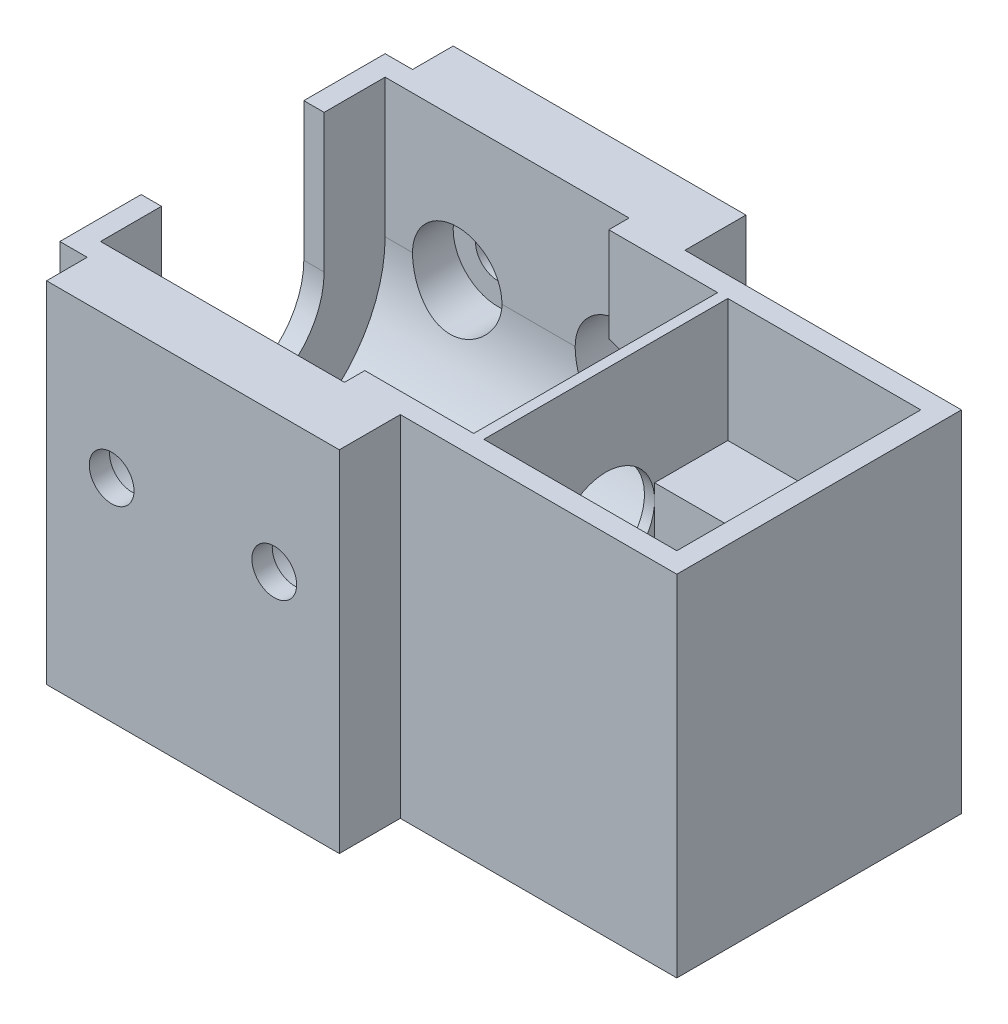
SolidWorks part; units mm, degrees
ref_plane "Front Plane" through (0, 0, 0) normal (0, 0, 1) x (1, 0, 0)
ref_plane "Top Plane" through (0, 0, 0) normal (0, 1, 0) x (1, 0, 0)
ref_plane "Right Plane" through (0, 0, 0) normal (1, 0, 0) x (0, 0, -1)
sketch "Sketch1" plane through (0, 0, 0) normal (0, 0, 1) x (1, 0, 0)
  line L1 (-76.2, -50.8) -> (40.64, -50.8)
  line L2 (-76.2, -50.8) -> (-76.2, 0)
  line L3 (-76.2, 0) -> (40.64, 0)
  line L4 (40.64, -50.8) -> (40.64, 0)
  line L5 (-76.2, -50.8) -> (40.64, 0) construction
  line L6 (-76.2, 0) -> (40.64, -50.8) construction
  point P0 (0, 0)
  dimension "D1" = 116.84
  dimension "D2" = 50.8
  dimension "D3" = 76.2
extrude "Boss-Extrude1" add sketch "Sketch1" along normal mid plane 63.5
sketch "Sketch2" plane through (0, 0, 0) normal (0, 0, 1) x (1, 0, 0)
  line L0 (-152.4829, -25.4) -> (6.8382, -25.4) construction
  line L1 (-49.3609, -3.175) -> (-49.3609, -12.7)
  line L2 (40.64, 0) -> (-76.2, 0) construction
  line L3 (40.64, 0) -> (-76.2, 0) construction
  line L4 (-11.2609, -3.175) -> (-11.2609, -6.35)
  line L5 (-11.2609, -25.4) -> (-11.2609, -3.175) construction
  line L6 (-128.4172, -25.4) -> (-157.8092, -25.4)
  line L7 (6.8382, -25.4) -> (40.64, -25.4)
  line L8 (-607.3619, -25.4) -> (6.8382, -25.4) construction
  line L9 (-49.3609, -3.175) -> (-11.2609, -3.175)
  line L10 (6.8382, -25.4) -> (-128.4172, -25.4)
  line L11 (-11.2609, -6.35) -> (5.7391, -6.35)
  line L12 (5.7391, -6.35) -> (5.7391, -17.78)
  line L13 (5.7391, -17.78) -> (23.7391, -17.78)
  line L14 (-49.3609, -12.7) -> (-220.2024, -12.7)
  line L15 (-220.2024, -12.7) -> (-220.2024, -25.4)
  line L16 (-220.2024, -25.4) -> (-157.8092, -25.4)
  line L17 (23.7391, -17.78) -> (23.7391, -25.4) construction
  line L18 (23.7391, -17.78) -> (40.64, -17.78)
  line L19 (40.64, -50.8) -> (40.64, 0) construction
  line L20 (40.64, -17.78) -> (40.64, -25.4)
  line L21 (-76.2, 0) -> (-76.2, -50.8) construction
  point P23 (-11.2609, -25.4)
  dimension "D1" = 22.225
  dimension "D2" = 38.1
  dimension "D3" = 25.4
  dimension "D4" = 35
  dimension "D5" = 7.62
  dimension "D6" = 3.175
  dimension "D7" = 26.8391
  dimension "D8" = 18
  dimension "D9" = 12.7
revolve "Cut-Revolve1" cut sketch "Sketch2" angle 360 about L0
sketch "Sketch38" plane through (40.64, 0, 0) normal (1, 0, 0) x (0, 0, -1)
  line L1 (-10, -35.4) -> (10, -35.4)
  line L2 (-10, -35.4) -> (-10, -15.4)
  line L3 (-10, -15.4) -> (10, -15.4)
  line L4 (10, -35.4) -> (10, -15.4)
  line L5 (-10, -35.4) -> (10, -15.4) construction
  line L6 (-10, -15.4) -> (10, -35.4) construction
  point P0 (0, -25.4)
  point P1 (0, -25.4)
  dimension "D1" = 20
  dimension "D2" = 20
extrude "Cut-Extrude33" cut sketch "Sketch38" against normal offset from surface (33.3134 mm away) 1.5875 up to face at (5.7391, -44.45, 0)
sketch "Sketch37" plane through (40.64, 0, 0) normal (1, 0, 0) x (0, 0, -1)
  line L0 (31.75, -50.8) -> (31.75, 0) construction
  line L1 (-31.75, 0) -> (31.75, 0)
  line L2 (-31.75, 0) -> (-31.75, -25.4)
  line L3 (-31.75, -25.4) -> (31.75, -25.4)
  line L4 (31.75, 0) -> (31.75, -25.4)
  line L5 (10, -35.4) -> (10, -15.4) construction
  point P7 (0, -25.4)
  point P11 (0, 0)
  point P14 (10, -25.4)
extrude "Cut-Extrude32" cut sketch "Sketch37" against normal through all
sketch "Sketch39" plane through (0, -25.4, 0) normal (0, 1, 0) x (1, 0, 0)
  line L10 (-76.2, 12.7) -> (-49.3609, 12.7)
  line L11 (-49.3609, 12.7) -> (-49.3609, 22.225)
  line L12 (-49.3609, 22.225) -> (-11.2609, 22.225)
  line L13 (-11.2609, 22.225) -> (-11.2609, 19.05)
  line L14 (-11.2609, 19.05) -> (5.7391, 19.05)
  line L15 (5.7391, 19.05) -> (5.7391, 7.62)
  line L16 (5.7391, 19.05) -> (5.7391, 7.62)
  line L17 (40.64, 10) -> (40.64, 31.75)
  line L18 (40.64, 31.75) -> (-76.2, 31.75)
  line L19 (-76.2, 31.75) -> (-76.2, 12.7)
  line L20 (-76.2, 12.7) -> (-49.3609, 12.7)
  line L21 (-49.3609, 12.7) -> (-49.3609, 22.225)
  line L22 (-49.3609, 22.225) -> (-11.2609, 22.225)
  line L23 (-11.2609, 22.225) -> (-11.2609, 19.05)
  line L24 (-11.2609, 19.05) -> (5.7391, 19.05)
  line L25 (7.3266, 10) -> (40.64, 10)
  line L26 (7.3266, 10) -> (40.64, 10)
  line L27 (40.64, 10) -> (40.64, 31.75)
  line L28 (40.64, 31.75) -> (-76.2, 31.75)
  line L29 (-76.2, 31.75) -> (-76.2, 12.7)
  line L30 (-49.3609, -12.7) -> (-76.2, -12.7)
  line L31 (-76.2, -12.7) -> (-76.2, -31.75)
  line L32 (-76.2, -31.75) -> (40.64, -31.75)
  line L33 (40.64, -31.75) -> (40.64, -10)
  line L34 (40.64, -10) -> (7.3266, -10)
  line L35 (40.64, -10) -> (7.3266, -10)
  line L36 (5.7391, -19.05) -> (-11.2609, -19.05)
  line L37 (-11.2609, -19.05) -> (-11.2609, -22.225)
  line L38 (-11.2609, -22.225) -> (-49.3609, -22.225)
  line L39 (-49.3609, -22.225) -> (-49.3609, -12.7)
  line L40 (-49.3609, -12.7) -> (-76.2, -12.7)
  line L41 (-76.2, -12.7) -> (-76.2, -31.75)
  line L42 (-76.2, -31.75) -> (40.64, -31.75)
  line L43 (40.64, -31.75) -> (40.64, -10)
  line L44 (5.7391, -7.62) -> (5.7391, -19.05)
  line L45 (5.7391, -7.62) -> (5.7391, -19.05)
  line L46 (5.7391, -19.05) -> (-11.2609, -19.05)
  line L47 (-11.2609, -19.05) -> (-11.2609, -22.225)
  line L48 (-11.2609, -22.225) -> (-49.3609, -22.225)
  line L49 (-49.3609, -22.225) -> (-49.3609, -12.7)
  line L52 (5.7391, 7.62) -> (7.3266, 7.62)
  line L53 (5.7391, 7.62) -> (7.3266, 7.62)
  line L54 (7.3266, 7.62) -> (7.3266, 10)
  line L55 (7.3266, 7.62) -> (7.3266, 10)
  line L56 (7.3266, -10) -> (7.3266, -7.62)
  line L57 (7.3266, -10) -> (7.3266, -7.62)
  line L58 (7.3266, -7.62) -> (5.7391, -7.62)
  line L59 (7.3266, -7.62) -> (5.7391, -7.62)
  dimension "D1" = 0
  dimension "D2" = 0
extrude "Boss-Extrude5" add sketch "Sketch39" along normal blind 25.4
sketch "Sketch40" plane through (0, 0, 0) normal (0, 1, 0) x (1, 0, 0)
  line L0 (7.3266, 10) -> (40.64, 10) construction
  line L1 (23.7391, 10) -> (40.64, 10)
  line L2 (23.7391, 10) -> (23.7391, -10)
  line L3 (23.7391, -10) -> (40.64, -10)
  line L4 (40.64, 10) -> (40.64, -10)
  line L6 (-11.2609, 22.225) -> (-11.2609, 19.05) construction
  dimension "D1" = 35
extrude "Boss-Extrude6" add sketch "Sketch40" against normal up to next
sketch "Sketch41" plane through (0, 0, 0) normal (0, 1, 0) x (1, 0, 0)
  line L2 (-76.2, 12.7) -> (-76.2, -12.7) construction
  circle A0 centre (-57.15, 0) radius 3.1134
  circle A1 centre (-31.75, 0) radius 3.1134
  circle A2 centre (-6.35, 0) radius 3.1134
  dimension "D1" = 19.05
extrude "Cut-Extrude34" cut sketch "Sketch41" against normal through all
ref_plane "Plane_Mid" through (0, -25.4, 0) normal (0, 1, 0) x (1, 0, 0)
ref_axis "Axis1" through (7.3266, -25.4, 0) along (-1, 0, 0)
sketch "Sketch42" plane through (0, 0, 0) normal (0, 0, 1) x (1, 0, 0)
  line L0 (1.7462, -25.4) -> (-1.7462, -25.4) construction
  line L1 (-76.2, 0) -> (-76.2, -25.4) construction
  circle A0 centre (-38.1, -25.4) radius 3.4925
  circle A1 centre (-12.7, -25.4) radius 3.4925
  dimension "D1" = 6.985
  dimension "D2" = 38.1
extrude "Cut-Extrude35" cut sketch "Sketch42" against normal through all both and the other way through all
sketch "Sketch43" plane through (0, 0, 0) normal (0, 0, 1) x (1, 0, 0)
  circle A0 centre (-38.1, -25.4) radius 6.985
  circle A1 centre (-12.7, -25.4) radius 6.985
  dimension "D1" = 13.97
extrude "Cut-Extrude36" cut sketch "Sketch43" against normal offset from surface (28.575 mm away) 3.175 up to face at (-9.2075, -25.4, -31.75)
extrude "Cut-Extrude37" cut sketch "Sketch43<2>" along normal offset from surface (28.575 mm away) 3.175 up to face at (-9.2075, -25.4, 31.75)
sketch "Sketch43<2>" plane through (0, 0, 0) normal (0, 0, 1) x (1, 0, 0) same geometry as "Sketch43"
sketch "Sketch44" plane through (0, 0, 0) normal (0, 1, 0) x (1, 0, 0)
  line L0 (5.7391, -19.05) -> (-11.2609, -19.05) construction
  line L1 (7.3266, 19.05) -> (23.2391, 19.05)
  line L2 (7.3266, 19.05) -> (7.3266, -19.05)
  line L3 (7.3266, -19.05) -> (23.2391, -19.05)
  line L4 (23.2391, 19.05) -> (23.2391, -19.05)
  line L5 (-11.2609, 19.05) -> (5.7391, 19.05) construction
  line L6 (7.3266, 7.62) -> (7.3266, 10) construction
  line L7 (23.7391, 10) -> (23.7391, -10) construction
  dimension "D1" = 0.5
extrude "Cut-Extrude38" cut sketch "Sketch44" against normal up to surface (35.4 mm away) up to face at (15.5329, -35.4, 0)
sketch "Sketch45" plane through (0, 0, 0) normal (0, 0, 1) x (1, 0, 0)
  line L0 (40.64, 0) -> (-76.2, 0) construction
  line L2 (37.465, 0) -> (23.2391, 0)
  line L4 (37.465, 0) -> (37.465, -15.4)
  line L5 (37.465, -15.4) -> (23.2391, -15.4)
  line L8 (23.2391, 0) -> (23.2391, -15.4)
  line L9 (40.64, -50.8) -> (40.64, 0) construction
  line L10 (23.2391, -35.4) -> (23.2391, 0) construction
  line L11 (-5.715, -25.4) -> (5.7391, -25.4) construction
  dimension "D1" = 3.175
  dimension "D2" = 10
extrude "Cut-Extrude39" cut sketch "Sketch45" against normal up to surface and the other way up to surface up to face at (15.2828, -17.7, -19.05) other way up to face at (15.2828, -17.7, 19.05)
sketch "Sketch46" plane through (0, 0, 0) normal (0, 1, 0) x (1, 0, 0)
  line L0 (-11.2609, 19.05) -> (5.7391, 19.05) construction
  line L1 (40.64, 31.75) -> (-2.54, 31.75)
  line L2 (40.64, 31.75) -> (40.64, 22.225)
  line L3 (40.64, 22.225) -> (-2.54, 22.225)
  line L4 (-2.54, 31.75) -> (-2.54, 22.225)
  line L5 (-76.2, 0) -> (40.64, 0) construction
  line L6 (-76.2, 12.7) -> (-76.2, -12.7) construction
  line L7 (40.64, -31.75) -> (40.64, 31.75) construction
  line L8 (40.64, -31.75) -> (40.64, -22.225)
  line L9 (40.64, -22.225) -> (-2.54, -22.225)
  line L10 (40.64, -31.75) -> (-2.54, -31.75)
  line L11 (-2.54, -31.75) -> (-2.54, -22.225)
  line L12 (-49.3609, 22.225) -> (-11.2609, 22.225) construction
  line L13 (-76.2, 31.75) -> (-48.26, 31.75)
  line L14 (-76.2, 31.75) -> (-76.2, 25.4)
  line L15 (-76.2, 25.4) -> (-48.26, 25.4)
  line L16 (-48.26, 31.75) -> (-48.26, 25.4)
  line L17 (-48.26, -31.75) -> (-48.26, -25.4)
  line L18 (-76.2, -25.4) -> (-48.26, -25.4)
  line L19 (-76.2, -31.75) -> (-76.2, -25.4)
  line L20 (-76.2, -31.75) -> (-48.26, -31.75)
  dimension "D1" = 3.175
  dimension "D2" = 3.175
  dimension "D3" = 3.175
  dimension "D4" = 3.175
extrude "Cut-Extrude40" cut sketch "Sketch46" against normal through all
sketch "Sketch49" plane through (0, 0, 0) normal (0, 1, 0) x (1, 0, 0)
  line L0 (-48.26, -25.4) -> (-76.2, -25.4) construction
  line L1 (-76.2, 25.4) -> (-52.5359, 25.4)
  line L2 (-76.2, 25.4) -> (-76.2, -25.4)
  line L3 (-76.2, -25.4) -> (-52.5359, -25.4)
  line L4 (-52.5359, 25.4) -> (-52.5359, -25.4)
  line L5 (-49.3609, -22.225) -> (-49.3609, 22.225) construction
  dimension "D1" = 3.175
extrude "Cut-Extrude42" cut sketch "Sketch49" against normal through all
sketch "Sketch50" plane through (0, 0, 0) normal (0, 1, 0) x (1, 0, 0)
  line L0 (-2.54, 22.225) -> (40.64, 22.225) construction
  line L1 (22.9851, 20.701) -> (23.2391, 20.701)
  line L2 (22.9851, 20.701) -> (22.9851, 22.225)
  line L3 (22.9851, 22.225) -> (23.2391, 22.225)
  line L4 (23.2391, 20.701) -> (23.2391, 22.225)
  line L5 (23.1121, 22.225) -> (23.1121, 20.701) construction
  line L6 (22.9851, 21.463) -> (23.2391, 21.463) construction
  line L8 (23.2391, 10) -> (23.2391, 19.05) construction
  line L9 (21.4611, 20.701) -> (21.7151, 20.701)
  line L10 (21.7151, 20.701) -> (21.7151, 22.225)
  line L11 (21.4611, 22.225) -> (21.7151, 22.225)
  line L12 (21.4611, 20.701) -> (21.4611, 22.225)
  line L13 (19.9371, 20.701) -> (20.1911, 20.701)
  line L14 (20.1911, 20.701) -> (20.1911, 22.225)
  line L15 (19.9371, 22.225) -> (20.1911, 22.225)
  line L16 (19.9371, 20.701) -> (19.9371, 22.225)
  line L17 (18.4131, 20.701) -> (18.6671, 20.701)
  line L18 (18.6671, 20.701) -> (18.6671, 22.225)
  line L19 (18.4131, 22.225) -> (18.6671, 22.225)
  line L20 (18.4131, 20.701) -> (18.4131, 22.225)
  line L21 (16.8891, 20.701) -> (17.1431, 20.701)
  line L22 (17.1431, 20.701) -> (17.1431, 22.225)
  line L23 (16.8891, 22.225) -> (17.1431, 22.225)
  line L24 (16.8891, 20.701) -> (16.8891, 22.225)
  line L25 (15.3651, 20.701) -> (15.6191, 20.701)
  line L26 (15.6191, 20.701) -> (15.6191, 22.225)
  line L27 (15.3651, 22.225) -> (15.6191, 22.225)
  line L28 (15.3651, 20.701) -> (15.3651, 22.225)
  line L29 (13.8411, 20.701) -> (14.0951, 20.701)
  line L30 (14.0951, 20.701) -> (14.0951, 22.225)
  line L31 (13.8411, 22.225) -> (14.0951, 22.225)
  line L32 (13.8411, 20.701) -> (13.8411, 22.225)
  line L33 (12.3171, 20.701) -> (12.5711, 20.701)
  line L34 (12.5711, 20.701) -> (12.5711, 22.225)
  line L35 (12.3171, 22.225) -> (12.5711, 22.225)
  line L36 (12.3171, 20.701) -> (12.3171, 22.225)
  line L37 (10.7931, 20.701) -> (11.0471, 20.701)
  line L38 (11.0471, 20.701) -> (11.0471, 22.225)
  line L39 (10.7931, 22.225) -> (11.0471, 22.225)
  line L40 (10.7931, 20.701) -> (10.7931, 22.225)
  line L41 (9.2691, 20.701) -> (9.5231, 20.701)
  line L42 (9.5231, 20.701) -> (9.5231, 22.225)
  line L43 (9.2691, 22.225) -> (9.5231, 22.225)
  line L44 (9.2691, 20.701) -> (9.2691, 22.225)
  point P0 (23.1121, 21.463)
  dimension "D1" = 0.254
  dimension "D2" = 1.524
  dimension "D3" = 10
extrude "Cut-Extrude43" cut sketch "Sketch50" against normal blind 2.54
sketch "Sketch52" plane through (23.7391, 0, 0) normal (-1, 0, 0) x (0, 0, 1)
  circle A0 centre (0, -25.4) radius 0.3175
  dimension "D1" = 0.635
extrude "Cut-Extrude45" cut sketch "Sketch52" against normal blind 0.0508
sketch "Sketch53" plane through (23.7391, 0, 0) normal (-1, 0, 0) x (0, 0, 1)
  circle A0 centre (0, -25.4) radius 2
  dimension "D1" = 4
extrude "Cut-Extrude46" cut sketch "Sketch53" against normal blind 0.0254
sketch "Sketch54" plane through (0, -35.4, 0) normal (0, 1, 0) x (1, 0, 0)
  line L0 (23.2391, 10) -> (23.2391, -10)
  line L8 (23.7391, 10) -> (23.2391, 10)
  line L9 (23.2391, 10) -> (23.2391, 19.05)
  line L10 (23.2391, 19.05) -> (7.3266, 19.05)
  line L11 (7.3266, 19.05) -> (7.3266, -19.05)
  line L12 (7.3266, -19.05) -> (23.2391, -19.05)
  line L13 (23.2391, -19.05) -> (23.2391, -10)
  line L14 (23.2391, -10) -> (23.7391, -10)
  line L15 (23.7391, -10) -> (23.7391, 10)
  line L17 (23.2391, 10) -> (23.2391, 19.05)
  line L18 (23.2391, 19.05) -> (7.3266, 19.05)
  line L19 (7.3266, 19.05) -> (7.3266, -19.05)
  line L20 (7.3266, -19.05) -> (23.2391, -19.05)
  line L21 (23.2391, -19.05) -> (23.2391, -10)
  dimension "D1" = 0
extrude "Boss-Extrude7" add sketch "Sketch54" along normal blind 2.54
sketch "Sketch55" plane through (0, -32.86, 0) normal (0, 1, 0) x (1, 0, 0)
  line L0 (23.2391, -19.05) -> (23.2391, -10) construction
  line L1 (23.2391, 10) -> (7.3266, 10)
  line L2 (23.2391, 10) -> (23.2391, 19.05)
  line L3 (23.2391, 19.05) -> (7.3266, 19.05)
  line L4 (7.3266, 10) -> (7.3266, 19.05)
  line L5 (23.2391, 10) -> (7.3266, 19.05) construction
  line L6 (23.2391, 19.05) -> (7.3266, 10) construction
  line L7 (7.3266, -19.05) -> (23.2391, -19.05)
  line L8 (7.3266, -19.05) -> (7.3266, -10)
  line L9 (7.3266, -10) -> (23.2391, -10)
  line L10 (23.2391, -19.05) -> (23.2391, -10)
  line L11 (7.3266, -19.05) -> (23.2391, -10) construction
  line L12 (7.3266, -10) -> (23.2391, -19.05) construction
  point P4 (15.2828, 14.525)
  point P11 (15.2828, -14.525)
extrude "Boss-Extrude8" add sketch "Sketch55" along normal up to surface (17.46 mm away) up to face at (26.9206, -15.4, 0)
sketch "Sketch57" plane through (0, -15.4, 0) normal (0, 1, 0) x (1, 0, 0)
  line L8 (23.7391, -10) -> (7.3266, -10)
  line L9 (7.3266, -10) -> (7.3266, -19.05)
  line L10 (7.3266, -19.05) -> (37.465, -19.05)
  line L11 (37.465, -19.05) -> (37.465, 19.05)
  line L12 (37.465, 19.05) -> (7.3266, 19.05)
  line L13 (23.7391, -10) -> (7.3266, -10)
  line L14 (7.3266, 19.05) -> (7.3266, 10)
  line L15 (23.7391, 10) -> (23.7391, -10)
  line L16 (7.3266, 19.05) -> (7.3266, 10)
  line L17 (7.3266, -10) -> (7.3266, -19.05)
  line L18 (7.3266, -19.05) -> (37.465, -19.05)
  line L19 (37.465, -19.05) -> (37.465, 19.05)
  line L20 (37.465, 19.05) -> (7.3266, 19.05)
  line L21 (7.3266, 10) -> (23.7391, 10)
  line L22 (7.3266, 10) -> (23.7391, 10)
  line L23 (23.7391, 10) -> (23.7391, -10)
  dimension "D1" = 0
extrude "Cut-Extrude47" cut sketch "Sketch57" against normal blind 7.62
sketch "Sketch58" plane through (0, -50.8, 0) normal (0, -1, 0) x (1, 0, 0)
  line L12 (-48.26, 25.4) -> (-52.5359, 25.4)
  line L13 (-52.5359, 25.4) -> (-52.5359, -25.4)
  line L14 (-52.5359, -25.4) -> (-48.26, -25.4)
  line L15 (-48.26, -25.4) -> (-48.26, -31.75)
  line L16 (-48.26, -31.75) -> (-2.54, -31.75)
  line L17 (-2.54, -31.75) -> (-2.54, -22.225)
  line L18 (-2.54, -22.225) -> (40.64, -22.225)
  line L19 (40.64, -22.225) -> (40.64, 22.225)
  line L20 (40.64, 22.225) -> (-2.54, 22.225)
  line L21 (-2.54, 22.225) -> (-2.54, 31.75)
  line L22 (-2.54, 31.75) -> (-48.26, 31.75)
  line L23 (-48.26, 31.75) -> (-48.26, 25.4)
  line L24 (-48.26, 25.4) -> (-52.5359, 25.4)
  line L25 (-52.5359, 25.4) -> (-52.5359, -25.4)
  line L26 (-52.5359, -25.4) -> (-48.26, -25.4)
  line L27 (-48.26, -25.4) -> (-48.26, -31.75)
  line L28 (-48.26, -31.75) -> (-2.54, -31.75)
  line L29 (-2.54, -31.75) -> (-2.54, -22.225)
  line L30 (-2.54, -22.225) -> (40.64, -22.225)
  line L31 (40.64, -22.225) -> (40.64, 22.225)
  line L32 (40.64, 22.225) -> (-2.54, 22.225)
  line L33 (-2.54, 22.225) -> (-2.54, 31.75)
  line L34 (-2.54, 31.75) -> (-48.26, 31.75)
  line L35 (-48.26, 31.75) -> (-48.26, 25.4)
  circle A0 centre (-31.75, 0) radius 3.1134
  circle A1 centre (-6.35, 0) radius 3.1134
  circle A2 centre (-6.35, 0) radius 3.1134 construction
  circle A3 centre (-31.75, 0) radius 3.1134 construction
  dimension "D1" = 0
extrude "Boss-Extrude10" add sketch "Sketch58" along normal blind 7.62
sketch "Sketch59" plane through (0, -35.4, 0) normal (0, 1, 0) x (1, 0, 0)
  line L4 (23.2391, 10) -> (23.2391, -10)
  line L5 (23.2391, -10) -> (23.7391, -10)
  line L6 (23.7391, -10) -> (23.7391, 10)
  line L7 (23.7391, 10) -> (23.2391, 10)
  line L8 (23.2391, 10) -> (23.2391, -10)
  line L9 (23.2391, -10) -> (23.7391, -10)
  line L10 (23.7391, -10) -> (23.7391, 10)
  line L11 (23.7391, 10) -> (23.2391, 10)
  dimension "D1" = 0
extrude "Cut-Extrude48" cut sketch "Sketch59" against normal blind 7.62
sketch "Sketch51" plane through (0, -23.02, 0) normal (0, 1, 0) x (1, 0, 0)
  line L0 (25.098, 0.254) -> (26.1082, 0.254)
  line L1 (24.59, 2.54) -> (25.098, 2.54)
  line L2 (24.59, 2.54) -> (24.59, 0.254)
  line L3 (24.59, -2.54) -> (25.098, -2.54)
  line L4 (25.098, 2.54) -> (25.098, 0.254)
  line L5 (29.6527, -0.254) -> (30.6629, -0.254)
  line L6 (25.098, -0.254) -> (25.098, -2.54)
  line L7 (26.6162, 2.54) -> (26.6162, 0.254)
  line L8 (26.1082, 2.54) -> (26.6162, 2.54)
  line L9 (26.1082, 2.54) -> (26.1082, 0.254)
  line L10 (26.1082, -2.54) -> (26.6162, -2.54)
  line L11 (28.1344, 2.54) -> (28.1344, 0.254)
  line L12 (27.6264, 2.54) -> (28.1344, 2.54)
  line L13 (27.6264, 2.54) -> (27.6264, 0.254)
  line L14 (27.6264, -2.54) -> (28.1344, -2.54)
  line L15 (29.6527, 2.54) -> (29.6527, 0.254)
  line L16 (29.1447, 2.54) -> (29.6527, 2.54)
  line L17 (29.1447, 2.54) -> (29.1447, 0.254)
  line L18 (29.1447, -2.54) -> (29.6527, -2.54)
  line L19 (31.1709, 2.54) -> (31.1709, 0.254)
  line L20 (30.6629, 2.54) -> (31.1709, 2.54)
  line L21 (30.6629, 2.54) -> (30.6629, 0.254)
  line L22 (30.6629, -2.54) -> (31.1709, -2.54)
  line L23 (32.6891, 2.54) -> (32.6891, 0.254)
  line L24 (32.1811, 2.54) -> (32.6891, 2.54)
  line L25 (32.1811, 2.54) -> (32.1811, 0.254)
  line L26 (32.1811, -2.54) -> (32.6891, -2.54)
  line L27 (34.2073, 2.54) -> (34.2073, 0.254)
  line L28 (33.6993, 2.54) -> (34.2073, 2.54)
  line L29 (33.6993, 2.54) -> (33.6993, 0.254)
  line L30 (33.6993, -2.54) -> (34.2073, -2.54)
  line L31 (35.7255, 2.54) -> (35.7255, 0.254)
  line L32 (35.2175, 2.54) -> (35.7255, 2.54)
  line L33 (35.2175, 2.54) -> (35.2175, 0.254)
  line L34 (35.2175, -2.54) -> (35.7255, -2.54)
  line L35 (35.258, 2.5876) -> (24.581, 2.5876) construction
  line L36 (23.32, 11.7754) -> (37.465, 11.7754) construction
  line L37 (25.098, -0.254) -> (26.1082, -0.254)
  line L38 (23.7391, 10) -> (23.7391, -10) construction
  line L39 (37.465, -19.05) -> (37.465, 19.05) construction
  line L40 (23.7391, 0.254) -> (24.59, 0.254)
  line L41 (23.7391, 0.254) -> (23.7391, -0.254)
  line L42 (23.7391, -0.254) -> (24.59, -0.254)
  line L43 (37.465, 0.254) -> (37.465, -0.254)
  line L44 (31.1709, 0.254) -> (32.1811, 0.254)
  line L46 (24.59, -0.254) -> (24.59, -2.54)
  line L47 (26.1082, -0.254) -> (26.1082, -2.54)
  line L48 (26.6162, 0.254) -> (27.6264, 0.254)
  line L49 (26.6162, -0.254) -> (26.6162, -2.54)
  line L51 (26.6162, -0.254) -> (27.6264, -0.254)
  line L52 (27.6264, -0.254) -> (27.6264, -2.54)
  line L53 (28.1344, 0.254) -> (29.1447, 0.254)
  line L54 (28.1344, -0.254) -> (29.1447, -0.254)
  line L55 (28.1344, -0.254) -> (28.1344, -2.54)
  line L56 (29.1447, -0.254) -> (29.1447, -2.54)
  line L57 (29.6527, 0.254) -> (30.6629, 0.254)
  line L58 (31.1709, -0.254) -> (32.1811, -0.254)
  line L61 (29.6527, -0.254) -> (29.6527, -2.54)
  line L62 (30.6629, -0.254) -> (30.6629, -2.54)
  line L63 (31.1709, -0.254) -> (31.1709, -2.54)
  line L64 (32.1811, -0.254) -> (32.1811, -2.54)
  line L65 (32.6891, 0.254) -> (33.6993, 0.254)
  line L66 (32.6891, -0.254) -> (33.6993, -0.254)
  line L67 (32.6891, -0.254) -> (32.6891, -2.54)
  line L68 (33.6993, -0.254) -> (33.6993, -2.54)
  line L69 (34.2073, 0.254) -> (35.2175, 0.254)
  line L70 (34.2073, -0.254) -> (35.2175, -0.254)
  line L71 (34.2073, -0.254) -> (34.2073, -2.54)
  line L72 (35.2175, -0.254) -> (35.2175, -2.54)
  line L73 (35.7255, -0.254) -> (35.7255, -2.54)
  line L74 (35.7255, 0.254) -> (37.465, 0.254)
  line L75 (35.7255, -0.254) -> (37.465, -0.254)
  text T1 "<b>v9</b>"
  point P0 (24.717, 0)
  point P51 (30.3925, 0)
  point P52 (23.7391, 0)
  dimension "D1" = 0.508
  dimension "D2" = 5.08
  dimension "D3" = 1.5182
  dimension "D5" = 0.8419
  dimension "D6" = 0.508
  dimension "D4" = 8
extrude "Cut-Extrude44" cut sketch "Sketch51" against normal blind 0.635
sketch "Sketch60" plane through (0, 0, 0) normal (0, 1, 0) x (1, 0, 0)
  line L1 (-60.6783, -40.5295) -> (60.6783, -40.5295)
  line L2 (-60.6783, -40.5295) -> (-60.6783, 40.5295)
  line L3 (-60.6783, 40.5295) -> (60.6783, 40.5295)
  line L4 (60.6783, -40.5295) -> (60.6783, 40.5295)
  line L5 (0, 40.5295) -> (0, -40.5295) construction
  line L6 (-60.6783, 0) -> (60.6783, 0) construction
  point P0 (0, 0)
extrude "Cut-Extrude49" cut sketch "Sketch60" against normal blind 10.16
ref_plane "Plane_Bottom" through (0, -47.625, 0) normal (0, 1, 0) x (1, 0, 0)
ref_plane "Plane_Top" through (0, -3.81, 0) normal (0, 1, 0) x (1, 0, 0)
sketch "Sketch61" plane through (5.7391, 0, 0) normal (-1, 0, 0) x (0, 0, 1)
  circle A0 centre (0, -25.4) radius 7.62
  circle A1 centre (0, -25.4) radius 8.9762
extrude "Boss-Extrude11" add sketch "Sketch61" against normal up to surface (1.5875 mm away) up to face at (7.3266, -22.6511, -10.8884)
sketch "Sketch62" plane through (0, -10.16, 0) normal (0, 1, 0) x (1, 0, 0)
  line L1 (7.3266, 7.62) -> (5.7391, 7.62)
  line L2 (7.3266, 7.62) -> (7.3266, -7.62)
  line L3 (7.3266, -7.62) -> (5.7391, -7.62)
  line L4 (5.7391, 7.62) -> (5.7391, -7.62)
  line L5 (7.3266, 7.62) -> (5.7391, -7.62) construction
  line L6 (7.3266, -7.62) -> (5.7391, 7.62) construction
  point P4 (6.5328, 0)
extrude "Boss-Extrude12" add sketch "Sketch62" against normal up to next
sketch "Sketch64" plane through (0, -10.16, 0) normal (0, 1, 0) x (1, 0, 0)
  line L25 (37.465, 19.05) -> (7.3266, 19.05)
  line L26 (37.465, 19.05) -> (37.465, -19.05)
  line L27 (37.465, -19.05) -> (7.3266, -19.05)
  line L28 (7.3266, 19.05) -> (7.3266, -19.05)
  line L29 (37.465, 19.05) -> (7.3266, -19.05) construction
  line L30 (37.465, -19.05) -> (7.3266, 19.05) construction
  line L48 (-11.2609, 19.05) -> (5.7391, 19.05)
  line L49 (5.7391, 19.05) -> (5.7391, -19.05)
  line L50 (5.7391, -19.05) -> (-11.2609, -19.05)
  line L51 (-11.2609, -19.05) -> (-11.2609, -22.225)
  line L52 (-11.2609, -22.225) -> (-49.3609, -22.225)
  line L53 (-49.3609, -22.225) -> (-49.3609, -12.7)
  line L54 (-49.3609, -12.7) -> (-52.5359, -12.7)
  line L55 (-52.5359, -12.7) -> (-52.5359, -25.4)
  line L56 (-52.5359, -25.4) -> (-48.26, -25.4)
  line L57 (-48.26, -25.4) -> (-48.26, -31.75)
  line L58 (-48.26, -31.75) -> (-2.54, -31.75)
  line L59 (-2.54, -31.75) -> (-2.54, -22.225)
  line L60 (-2.54, -22.225) -> (40.64, -22.225)
  line L61 (40.64, -22.225) -> (40.64, 22.225)
  line L62 (40.64, 22.225) -> (-2.54, 22.225)
  line L63 (-2.54, 22.225) -> (-2.54, 31.75)
  line L64 (-2.54, 31.75) -> (-48.26, 31.75)
  line L65 (-48.26, 31.75) -> (-48.26, 25.4)
  line L66 (-48.26, 25.4) -> (-52.5359, 25.4)
  line L67 (-52.5359, 25.4) -> (-52.5359, 12.7)
  line L68 (-52.5359, 12.7) -> (-49.3609, 12.7)
  line L69 (-49.3609, 12.7) -> (-49.3609, 22.225)
  line L70 (-49.3609, 22.225) -> (-11.2609, 22.225)
  line L71 (-11.2609, 22.225) -> (-11.2609, 19.05)
  line L72 (-11.2609, 19.05) -> (5.7391, 19.05)
  line L73 (5.7391, 19.05) -> (5.7391, -19.05)
  line L74 (5.7391, -19.05) -> (-11.2609, -19.05)
  line L75 (-11.2609, -19.05) -> (-11.2609, -22.225)
  line L76 (-11.2609, -22.225) -> (-49.3609, -22.225)
  line L77 (-49.3609, -22.225) -> (-49.3609, -12.7)
  line L78 (-49.3609, -12.7) -> (-52.5359, -12.7)
  line L79 (-52.5359, -12.7) -> (-52.5359, -25.4)
  line L80 (-52.5359, -25.4) -> (-48.26, -25.4)
  line L81 (-48.26, -25.4) -> (-48.26, -31.75)
  line L82 (-48.26, -31.75) -> (-2.54, -31.75)
  line L83 (-2.54, -31.75) -> (-2.54, -22.225)
  line L84 (-2.54, -22.225) -> (40.64, -22.225)
  line L85 (40.64, -22.225) -> (40.64, 22.225)
  line L86 (40.64, 22.225) -> (-2.54, 22.225)
  line L87 (-2.54, 22.225) -> (-2.54, 31.75)
  line L88 (-2.54, 31.75) -> (-48.26, 31.75)
  line L89 (-48.26, 31.75) -> (-48.26, 25.4)
  line L90 (-48.26, 25.4) -> (-52.5359, 25.4)
  line L91 (-52.5359, 25.4) -> (-52.5359, 12.7)
  line L92 (-52.5359, 12.7) -> (-49.3609, 12.7)
  line L93 (-49.3609, 12.7) -> (-49.3609, 22.225)
  line L94 (-49.3609, 22.225) -> (-11.2609, 22.225)
  line L95 (-11.2609, 22.225) -> (-11.2609, 19.05)
  point P28 (22.3958, 0)
  dimension "D1" = 0
extrude "Boss-Extrude14" add sketch "Sketch64" along normal up to surface (6.35 mm away) up to plane "Plane_Top"
sketch "Sketch65" plane through (7.3266, 0, 0) normal (1, 0, 0) x (0, 0, -1)
  line L0 (-10, -23.02) -> (-7.62, -23.02)
  line L1 (10, -23.02) -> (7.62, -23.02)
  line L2 (-7.62, -32.86) -> (-7.62, -23.02)
  line L3 (7.62, -32.86) -> (7.62, -23.02)
  line L6 (-10, -23.02) -> (-10, -32.86)
  line L7 (-10, -32.86) -> (-7.62, -32.86)
  line L8 (7.62, -32.86) -> (10, -32.86)
  line L28 (10, -32.86) -> (10, -23.02)
  point P12 (8.81, -23.02)
extrude "Boss-Extrude16" add sketch "Sketch65" along normal up to next
sketch "Sketch66" plane through (0, -23.02, 0) normal (0, 1, 0) x (1, 0, 0)
  line L0 (23.2391, -7.62) -> (23.2391, 7.62) construction
  line L1 (23.7391, 10) -> (23.2391, 10)
  line L2 (23.7391, 10) -> (23.7391, -10)
  line L3 (23.7391, -10) -> (23.2391, -10)
  line L4 (23.2391, 10) -> (23.2391, -10)
  line L5 (23.7391, 10) -> (23.2391, -10) construction
  line L6 (23.7391, -10) -> (23.2391, 10) construction
  line L9 (7.3266, 0) -> (5.7391, 0) construction
  line L10 (23.7391, -0.254) -> (23.7391, -7.62) construction
  point P4 (23.4891, 0)
  dimension "D1" = 20
extrude "Cut-Extrude50" cut sketch "Sketch66" against normal up to surface (20 mm away) up to face at (23.4891, -43.02, 0)
